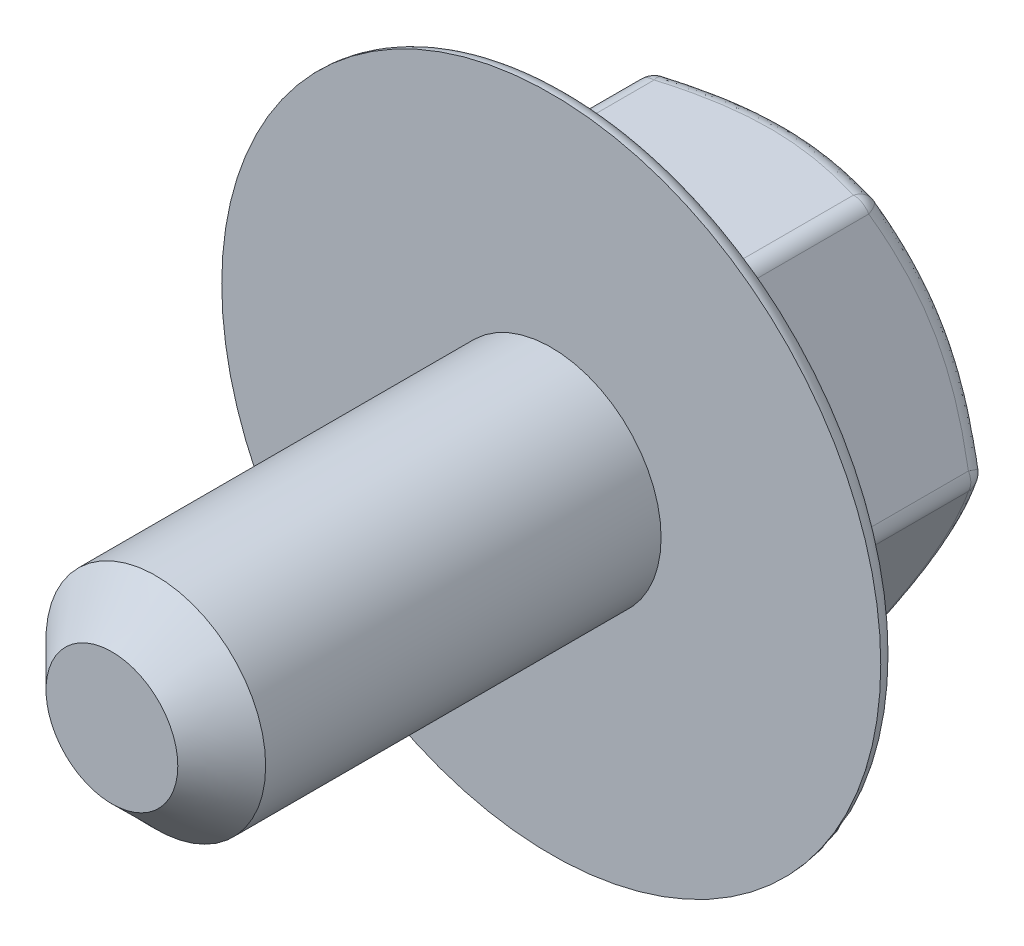
SolidWorks part; units mm, degrees
ref_plane "Front Plane" through (0, 0, 0) normal (0, 0, 1) x (1, 0, 0)
ref_plane "Top Plane" through (0, 0, 0) normal (0, 1, 0) x (1, 0, 0)
ref_plane "Right Plane" through (0, 0, 0) normal (1, 0, 0) x (0, 0, -1)
sketch "Sketch1" plane through (0, 0, 0) normal (0, 0, 1) x (1, 0, 0)
  line L1 (2.5, -4.3301) -> (5, 0)
  line L2 (5, 0) -> (2.5, 4.3301)
  line L3 (2.5, 4.3301) -> (-2.5, 4.3301)
  line L4 (-2.5, 4.3301) -> (-5, 0)
  line L5 (-5, 0) -> (-2.5, -4.3301)
  line L6 (-2.5, -4.3301) -> (2.5, -4.3301)
  circle A1 centre (0, 0) radius 4.3301 construction
  dimension "D1" = 10
extrude "Boss-Extrude1" add sketch "Sketch1" along normal blind 5
sketch "Sketch3" plane through (0, 0, 0) normal (0, 1, 0) x (1, 0, 0)
  line L0 (4, 0) -> (5, 0)
  line L1 (5, 0) -> (2.5, 0) construction
  line L2 (5, 0) -> (5, -0.6)
  line L3 (5, -5) -> (5, 0) construction
  line L4 (5, -0.6) -> (4, 0)
  line L5 (5, -2.5) -> (5.4945, -2.5) construction
  line L9 (0, 0) -> (0, -4.9238) construction
  dimension "D1" = 1
  dimension "D2" = 0.6
revolve "Cut-Revolve1" cut sketch "Sketch3" angle 360 about L9
sketch "Sketch4" plane through (0, 0, 0) normal (0, 0, -1) x (-1, 0, 0)
  circle A0 centre (0, 0) radius 4
extrude "Cut-Extrude2" cut sketch "Sketch4" against normal blind 0.1
sketch "Sketch5" plane through (0, 0, 5) normal (0, 0, 1) x (1, 0, 0)
  circle A0 centre (0, 0) radius 7.5
  dimension "D1" = 15
extrude "Boss-Extrude2" add sketch "Sketch5" along normal blind 0.4
fillet "Fillet6" radius 0.4 18 edges at (0, 4.3301, 5) (-0.2351, 4.3301, 0.2019) (3.75, 2.1651, 5) (2.5, 4.3301, 2.8) (3.8452, 2.0002, 0.2006) (3.75, -2.1651, 5) (5, 0, 2.8) (3.6548, -2.3299, 0.2006) (-3.75, -2.1651, 5) (-3.8452, -2.0002, 0.2006) (-2.5, -4.3301, 2.8) (0, -4.3301, 5) (2.5, -4.3301, 2.8) (0.2351, -4.3301, 0.2019) (-2.5, 4.3301, 2.8) (-3.75, 2.1651, 5) (-5, 0, 2.8) (-3.6548, 2.3299, 0.2006)
fillet "Fillet7" radius 0.4 1 edges at (7.5, 0, 5)
sketch "Sketch6" plane through (0, 0, 5.4) normal (0, 0, 1) x (1, 0, 0)
  circle A0 centre (0, 0) radius 2.5
  dimension "D1" = 5
extrude "Boss-Extrude3" add sketch "Sketch6" along normal blind 10
chamfer "Chamfer1" distance 1 1 edges at (2.5, 0, 15.4)
